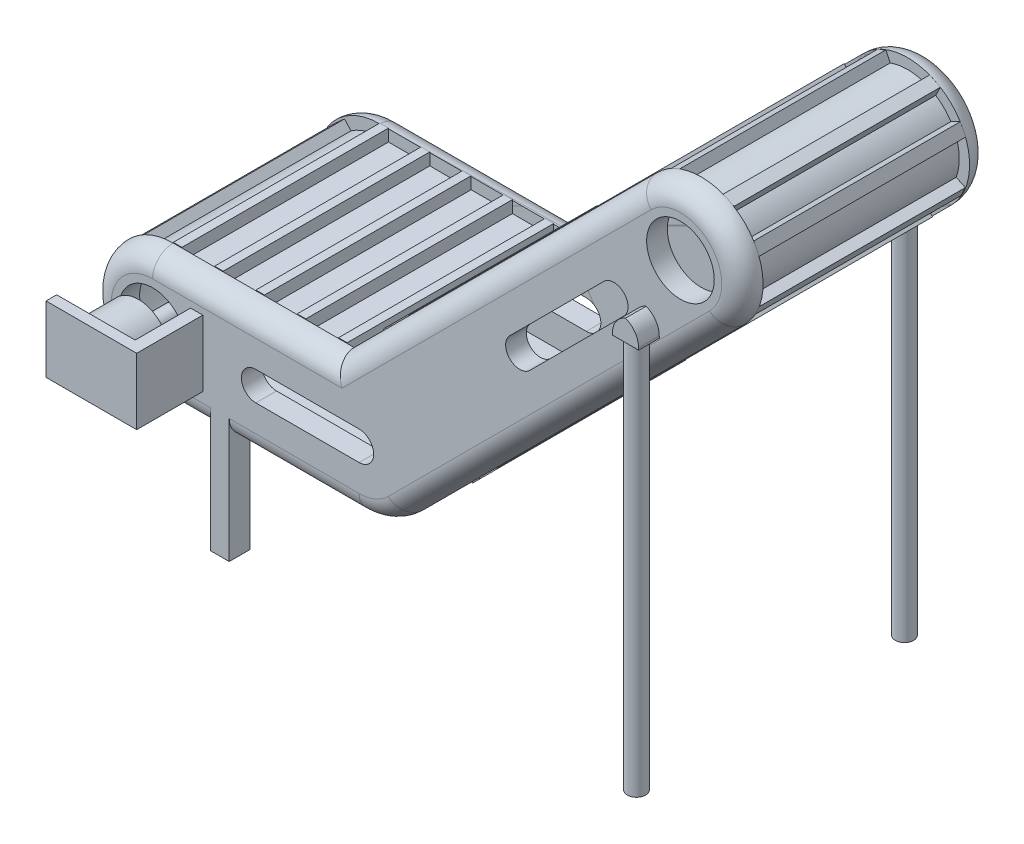
SolidWorks part; units mm, degrees
ref_plane "Front Plane" through (0, 0, 0) normal (0, 0, 1) x (1, 0, 0)
ref_plane "Top Plane" through (0, 0, 0) normal (0, 1, 0) x (1, 0, 0)
ref_plane "Right Plane" through (0, 0, 0) normal (1, 0, 0) x (0, 0, -1)
sketch "Sketch1" plane through (0, 0, 0) normal (0, 0, 1) x (1, 0, 0)
  line L0 (0, 0) -> (50, 0) construction
  line L1 (0, 15) -> (43.7868, 15)
  line L2 (0, -15) -> (50, -15)
  line L3 (50, 0) -> (127.7817, 77.7817) construction
  line L4 (43.7868, 15) -> (117.1751, 88.3883)
  line L5 (60.6066, -10.6066) -> (138.3883, 67.1751)
  line L6 (25, 0) -> (50, 0) construction
  line L7 (25, 3.5125) -> (50, 3.5125)
  line L8 (25, -3.5125) -> (50, -3.5125)
  line L9 (88.8909, 38.8909) -> (111.6659, 61.6659) construction
  line L10 (86.466, 41.3158) -> (109.241, 64.0908)
  line L11 (91.3158, 36.466) -> (114.0908, 59.241)
  arc A0 (0, 15) -> (0, -15) centre (0, 0) ccw
  arc A1 (50, -15) -> (60.6066, -10.6066) centre (50, 0) ccw
  arc A3 (138.3883, 67.1751) -> (117.1751, 88.3883) centre (127.7817, 77.7817) ccw
  arc A4 (50, -15) -> (60.6066, -10.6066) centre (50, 0) ccw
  circle A5 centre (0, 0) radius 8.1381
  circle A6 centre (127.7817, 77.7817) radius 8.1838
  arc A7 (25, 3.5125) -> (25, -3.5125) centre (25, 0) ccw
  arc A8 (50, -3.5125) -> (50, 3.5125) centre (50, 0) ccw
  arc A9 (86.466, 41.3158) -> (91.3158, 36.466) centre (88.8909, 38.8909) ccw
  arc A10 (114.0908, 59.241) -> (109.241, 64.0908) centre (111.6659, 61.6659) ccw
  point P3 (25, 0)
  point P10 (88.8909, 38.8909)
  point P17 (37.5, 0)
  point P22 (100.2784, 50.2784)
  dimension "D3" = 15
  dimension "D4" = 15
  dimension "D1" = 50
  dimension "D2" = 110
extrude "Boss-Extrude1" add sketch "Sketch1" along normal blind 5 contours L5 A3 L4 L1 A0 L2 A1 A10 L11 A9 L10 A8 L8 A7 L7 A6 A5
sketch "Sketch3" plane through (0, 15, 0) normal (0, 1, 0) x (1, 0, 0)
  line L0 (0, -5) -> (50, -5) construction
  line L1 (13.9802, -5) -> (18.5446, -5)
  line L2 (13.9802, -5) -> (13.9802, 0)
  line L3 (13.9802, 0) -> (18.5446, 0)
  line L4 (18.5446, -5) -> (18.5446, 0)
  line L5 (0, 0) -> (50, 0) construction
extrude "Boss-Extrude5" add sketch "Sketch3" against normal blind 55
fillet "Fillet1" radius 5 3 edges at (6.9901, -15, 5) (-15, 0, 5) (21.8934, 15, 5)
fillet "Fillet2" radius 5 5 edges at (34.2723, -15, 5) (55.7403, -13.8582, 5) (99.4975, 28.2843, 5) (138.3883, 88.3883, 5) (77.981, 49.1942, 5)
ref_plane "Plane2" through (0, 0, -25) normal (0, 0, 1) x (1, 0, 0)
mirror "Mirror6" about plane through (0, 0, -25) normal (0, 0, 1) of bodies 105
sketch "Sketch5" plane through (0, 0, -25) normal (0, 0, 1) x (1, 0, 0)
  line L0 (0, 0) -> (37.5139, 0) construction
  line L1 (2.0985, 12.2267) -> (10, 12.2267)
  line L2 (2.0985, -12.2286) -> (10, -12.2355)
  line L3 (50, 0) -> (127.7817, 77.7817) construction
  line L4 (49.3072, 16.934) -> (52.8392, 20.4682)
  line L5 (60.7195, -6.951) -> (65.1802, -2.4902)
  line L6 (0, 0) -> (37.5139, 0) construction
  line L7 (0, 10.7267) -> (37.5139, 10.7267)
  line L8 (0, -10.7267) -> (50.6802, -10.7267)
  line L9 (127.7817, 77.7817) -> (50, 0) construction
  line L11 (120.0072, 85.5563) -> (47.8481, 13.3972)
  line L12 (10, 12.2267) -> (10, 15.1579)
  line L14 (0, 12.2267) -> (0, 15.1579)
  line L15 (0, 15.1579) -> (2.0985, 15.1579)
  line L16 (2.0985, 12.2267) -> (2.0985, 15.1579)
  line L18 (12.0985, 12.2267) -> (12.0985, 15.1579)
  line L19 (10, 15.1579) -> (12.0985, 15.1579)
  line L20 (20, 12.2267) -> (20, 15.1579)
  line L22 (22.0985, 12.2267) -> (22.0985, 15.1579)
  line L23 (20, 15.1579) -> (22.0985, 15.1579)
  line L24 (30, 12.2267) -> (30, 15.1579)
  line L26 (32.0985, 12.2267) -> (32.0985, 15.1579)
  line L27 (30, 15.1579) -> (32.0985, 15.1579)
  line L28 (40, 12.2267) -> (40, 15.1579)
  line L29 (40, 12.2267) -> (40.4589, 12.2267)
  line L30 (42.0985, 12.2267) -> (42.0985, 15.1579)
  line L31 (40, 15.1579) -> (42.0985, 15.1579)
  line L32 (42.0985, -12.2267) -> (42.0985, -15.1579)
  line L33 (40, -15.1579) -> (42.0985, -15.1579)
  line L34 (40, -12.2267) -> (40, -15.1579)
  line L35 (30, -15.1579) -> (32.0985, -15.1579)
  line L36 (32.0985, -12.2267) -> (32.0985, -15.1579)
  line L37 (30, -12.2267) -> (30, -15.1579)
  line L38 (22.0985, -12.2267) -> (22.0985, -15.1579)
  line L39 (20, -15.1579) -> (22.0985, -15.1579)
  line L40 (20, -12.2267) -> (20, -15.1579)
  line L41 (12.0985, -12.2267) -> (12.0985, -15.1579)
  line L42 (10, -15.1579) -> (12.0985, -15.1579)
  line L43 (10, -12.2267) -> (10, -15.1579)
  line L44 (2.0985, -12.2267) -> (2.0985, -15.1579)
  line L45 (0, -12.2267) -> (0, -15.1579)
  line L46 (0, -15.1579) -> (2.0985, -15.1579)
  line L48 (47.5321, 15.1579) -> (46.0271, 16.662)
  line L49 (49.3072, 16.934) -> (47.8021, 18.4382)
  line L50 (46.0271, 16.662) -> (47.8021, 18.4382)
  line L52 (52.8392, 20.4682) -> (50.8757, 22.4305)
  line L53 (54.5966, 22.2267) -> (52.6331, 24.189)
  line L54 (50.8757, 22.4305) -> (52.6331, 24.189)
  line L56 (58.8352, 26.468) -> (56.9622, 28.3398)
  line L57 (62.0318, 29.6666) -> (60.1588, 31.5384)
  line L58 (56.9622, 28.3398) -> (60.1588, 31.5384)
  line L59 (67.1619, 34.7999) -> (65.2889, 36.6717)
  line L61 (65.2889, 36.6717) -> (67.1559, 38.5399)
  line L62 (69.0289, 36.6681) -> (67.1559, 38.5399)
  line L63 (74.4579, 42.1005) -> (72.5849, 43.9723)
  line L65 (72.5849, 43.9723) -> (74.7618, 46.1505)
  line L66 (76.6347, 44.2787) -> (74.7618, 46.1505)
  line L67 (81.8296, 49.4767) -> (79.9566, 51.3486)
  line L69 (79.9566, 51.3486) -> (81.7542, 53.1474)
  line L70 (83.6272, 51.2755) -> (81.7542, 53.1474)
  line L71 (88.8909, 56.5425) -> (87.0179, 58.4143)
  line L73 (87.0179, 58.4143) -> (88.8008, 60.1983)
  line L74 (90.6737, 58.3265) -> (88.8008, 60.1983)
  line L75 (96.4729, 64.1292) -> (94.5999, 66.001)
  line L77 (94.5999, 66.001) -> (96.2798, 67.682)
  line L78 (98.1528, 65.8101) -> (96.2798, 67.682)
  line L79 (104.322, 71.9833) -> (102.449, 73.8551)
  line L81 (102.449, 73.8551) -> (104.2537, 75.6608)
  line L82 (106.1266, 73.789) -> (104.2537, 75.6608)
  line L83 (112.3034, 79.9696) -> (110.4304, 81.8415)
  line L85 (110.4304, 81.8415) -> (112.418, 83.8303)
  line L86 (114.291, 81.9585) -> (112.418, 83.8303)
  line L88 (121.4099, 88.5298) -> (120.3652, 90.7497)
  line L89 (123.5609, 89.5421) -> (122.5162, 91.7619)
  line L90 (120.3652, 90.7497) -> (122.5162, 91.7619)
  line L92 (132.0026, 89.5421) -> (133.1346, 91.8248)
  line L93 (134.589, 88.2595) -> (135.7209, 90.5422)
  line L94 (133.1346, 91.8248) -> (135.7209, 90.5422)
  line L96 (-6.9861, 10.0343) -> (-8.5357, 11.76)
  line L97 (-9.2272, 8.022) -> (-10.7767, 9.7476)
  line L98 (-8.5357, 11.76) -> (-10.7767, 9.7476)
  line L100 (-12.1096, 1.6884) -> (-15.5831, 1.6884)
  line L101 (-12.1096, -1.6884) -> (-15.5831, -1.6884)
  line L102 (-15.5831, 1.6884) -> (-15.5831, -1.6884)
  line L104 (-10.7267, -5.8677) -> (-15.0566, -8.8817)
  line L105 (-9.2272, -8.022) -> (-13.5571, -11.0359)
  line L106 (-15.0566, -8.8817) -> (-13.5571, -11.0359)
  line L107 (65.1579, -2.4679) -> (66.662, -3.9729)
  line L108 (66.662, -3.9729) -> (68.4382, -2.1979)
  line L109 (66.934, -0.6928) -> (68.4382, -2.1979)
  line L110 (70.4682, 2.8392) -> (72.4305, 0.8757)
  line L111 (72.4305, 0.8757) -> (74.189, 2.6331)
  line L112 (72.2267, 4.5966) -> (74.189, 2.6331)
  line L113 (76.468, 8.8352) -> (78.3398, 6.9622)
  line L114 (78.3398, 6.9622) -> (81.5384, 10.1588)
  line L115 (79.6666, 12.0318) -> (81.5384, 10.1588)
  line L116 (99.4767, 31.8296) -> (101.3486, 29.9566)
  line L117 (101.3486, 29.9566) -> (103.1474, 31.7542)
  line L118 (101.2755, 33.6272) -> (103.1474, 31.7542)
  line L119 (106.5425, 38.8909) -> (108.4143, 37.0179)
  line L120 (108.4143, 37.0179) -> (110.1983, 38.8008)
  line L121 (108.3265, 40.6737) -> (110.1983, 38.8008)
  line L122 (114.1292, 46.4729) -> (116.001, 44.5999)
  line L123 (116.001, 44.5999) -> (117.682, 46.2798)
  line L124 (115.8101, 48.1528) -> (117.682, 46.2798)
  line L125 (121.9833, 54.322) -> (123.8551, 52.449)
  line L126 (123.8551, 52.449) -> (125.6608, 54.2537)
  line L127 (123.789, 56.1266) -> (125.6608, 54.2537)
  line L128 (129.9696, 62.3034) -> (131.8415, 60.4304)
  line L129 (131.8415, 60.4304) -> (133.8303, 62.418)
  line L130 (131.9585, 64.291) -> (133.8303, 62.418)
  line L131 (138.5298, 71.4099) -> (140.7497, 70.3652)
  line L132 (140.7497, 70.3652) -> (141.7619, 72.5162)
  line L133 (139.5421, 73.5609) -> (141.7619, 72.5162)
  line L134 (138.2595, 84.589) -> (140.5422, 85.7209)
  line L135 (141.8248, 83.1346) -> (140.5422, 85.7209)
  line L136 (139.5421, 82.0026) -> (141.8248, 83.1346)
  line L138 (84.7999, 17.1619) -> (86.6717, 15.2889)
  line L139 (86.6717, 15.2889) -> (88.5399, 17.1559)
  line L140 (86.6681, 19.0289) -> (88.5399, 17.1559)
  line L141 (92.1005, 24.4579) -> (93.9723, 22.5849)
  line L142 (93.9723, 22.5849) -> (96.1505, 24.7618)
  line L143 (94.2787, 26.6347) -> (96.1505, 24.7618)
  line L144 (58.8352, -8.8352) -> (60.6066, -10.6066)
  line L146 (60.6066, -10.6066) -> (62.4909, -8.7223)
  line L147 (60.7195, -6.951) -> (62.4909, -8.7223)
  line L148 (60.6066, -10.6066) -> (57.0711, -7.0711) construction
  line L149 (60.6066, -10.6066) -> (138.3883, 67.1751) construction
  line L150 (49.993, -12.2705) -> (50, -15)
  line L151 (52.3888, -12.2644) -> (52.548, -12.264)
  line L152 (50, -15) -> (52.5549, -14.9935)
  line L153 (52.548, -12.264) -> (52.5549, -14.9935)
  line L154 (50, -15) -> (50, -10) construction
  line L155 (12.0985, 12.2267) -> (20, 12.2267)
  line L156 (32.0985, 12.2267) -> (40.4589, 12.2267)
  line L157 (22.0985, 12.2267) -> (30, 12.2267)
  line L158 (54.5966, 22.2267) -> (58.8352, 26.468)
  line L159 (62.0318, 29.6666) -> (67.1619, 34.7999)
  line L160 (69.0289, 36.6681) -> (74.4579, 42.1005)
  line L161 (76.6347, 44.2787) -> (81.8296, 49.4767)
  line L162 (83.6272, 51.2755) -> (88.8909, 56.5425)
  line L163 (12.0985, -12.2373) -> (20, -12.2442)
  line L164 (22.0985, -12.2461) -> (30, -12.253)
  line L165 (32.0985, -12.2548) -> (40, -12.2618)
  line L166 (42.0985, -12.2636) -> (49.993, -12.2705)
  line L167 (66.9558, -0.7146) -> (70.4889, 2.8185)
  line L168 (72.2469, 4.5764) -> (76.4868, 8.8164)
  line L169 (79.6844, 12.014) -> (84.8161, 17.1457)
  line L170 (86.6837, 19.0133) -> (92.1144, 24.444)
  line L171 (94.2919, 26.6215) -> (99.4884, 31.8179)
  line L172 (101.2866, 33.6162) -> (106.5519, 38.8815)
  line L173 (108.3353, 40.6649) -> (114.1363, 46.4658)
  line L174 (115.8167, 48.1462) -> (121.9878, 54.3174)
  line L175 (123.793, 56.1226) -> (129.9717, 62.3013)
  line L176 (131.9599, 64.2895) -> (136.617, 68.9465)
  line L177 (90.6737, 58.3265) -> (96.4729, 64.1292)
  line L178 (98.1528, 65.8101) -> (104.322, 71.9833)
  line L179 (106.1266, 73.789) -> (112.3034, 79.9696)
  line L180 (114.291, 81.9585) -> (118.9287, 86.5991)
  line L181 (57.7513, -7.7978) -> (135.5563, 70.0072)
  arc A1 (0, 12.2267) -> (-6.9861, 10.0343) centre (0, 0) ccw
  arc A4 (136.617, 68.9465) -> (138.5298, 71.4099) centre (127.7817, 77.7817) ccw
  arc A5 (47.632, -12.2684) -> (49.9936, -12.4949) centre (50, 0) ccw
  arc A6 (0, 10.7267) -> (0, -10.7267) centre (0, 0) ccw
  arc A7 (39.2027, 10.593) -> (37.5139, 10.7267) centre (37.5139, 0) ccw
  arc A8 (135.5563, 70.0072) -> (120.0072, 85.5563) centre (127.7817, 77.7817) ccw
  arc A10 (47.8481, 13.3972) -> (39.2027, 10.593) centre (40.777, 20.4682) cw
  arc A11 (47.5321, 15.1579) -> (42.0985, 12.3621) centre (40.4589, 22.2267) cw
  arc A12 (57.7513, -7.7978) -> (50.6802, -10.7267) centre (50.6802, -0.7267) cw
  arc A13 (50, -15) -> (60.6066, -10.6066) centre (50, 0) ccw construction
  arc A14 (52.3888, -12.2644) -> (58.8352, -8.8352) centre (50, 0) ccw
  arc A15 (-9.2272, 8.022) -> (-12.1096, 1.6884) centre (0, 0) ccw
  arc A16 (-12.1096, -1.6884) -> (-10.7267, -5.8677) centre (0, 0) ccw
  arc A17 (-9.2272, -8.022) -> (0, -12.2267) centre (0, 0) ccw
  arc A18 (139.5421, 73.5609) -> (139.5421, 82.0026) centre (127.7817, 77.7817) ccw
  arc A19 (121.4099, 88.5298) -> (118.9287, 86.5991) centre (127.7817, 77.7817) ccw
  arc A20 (132.0026, 89.5421) -> (123.5609, 89.5421) centre (127.7817, 77.7817) ccw
  arc A21 (138.2595, 84.589) -> (134.589, 88.2595) centre (127.7817, 77.7817) ccw
  point P4 (25, 0)
  point P6 (18.7569, 0)
  point P12 (88.8909, 38.8909)
  point P21 (88.8909, 38.8909)
  dimension "D3" = 10
  dimension "D4" = 10
  dimension "D5" = 10
  dimension "D1" = 1.5
  dimension "D6" = 5
extrude "Boss-Extrude6" add sketch "Sketch5" against normal up to surface and the other way up to surface separate body contours L134 A21 L93 L94 L92 A20 L89 L90 L88 A19 L180 L86 L85 L83 L179 L82 L81 L79 L178 L78 L77 L75 L177 L74 L73 L71 L162 L70 L69 L67 L161 L66 L65 L63 L160 L62 L61 L59 L159 L57 L58 L56 L158 L53 L54 L52 L4 L49 L50 L48 A11
sketch "Sketch6" plane through (0, 0, 5) normal (0, 0, 1) x (1, 0, 0)
  line L1 (116.3232, 58.8688) -> (122.6501, 58.8688)
  line L2 (116.3232, 58.8688) -> (116.3232, 64.3521)
  line L3 (116.3232, 64.3521) -> (122.6501, 64.3521)
  line L4 (122.6501, 58.8688) -> (122.6501, 64.3521)
  line L5 (116.3232, 58.8688) -> (122.6501, 64.3521) construction
  line L6 (116.3232, 64.3521) -> (122.6501, 58.8688) construction
  point P0 (119.4866, 61.6104)
extrude "Boss-Extrude7" add sketch "Sketch6" along normal blind 5
fillet "Fillet4" radius 5 2 edges at (116.3232, 64.3521, 7.5) (122.6501, 64.3521, 7.5)
sketch "Sketch7" plane through (0, 58.8688, 0) normal (0, -1, 0) x (1, 0, 0)
  circle A0 centre (119.5759, 7.4319) radius 2.2161
extrude "Boss-Extrude8" add sketch "Sketch7" along normal blind 95
mirror "Mirror8" about plane through (0, 0, -25) normal (0, 0, 1) of bodies 110
sketch "Sketch8" plane through (0, 0, 5) normal (0, 0, 1) x (1, 0, 0)
  line L1 (9.1883, -7.5633) -> (12.1408, -7.5633)
  line L2 (9.1883, -7.5633) -> (9.1883, 8.4648)
  line L3 (9.1883, 8.4648) -> (12.1408, 8.4648)
  line L4 (12.1408, -7.5633) -> (12.1408, 8.4648)
extrude "Boss-Extrude12" add sketch "Sketch8" along normal blind 16
sketch "Sketch10" plane through (9.1883, 0, 0) normal (-1, 0, 0) x (0, 0, 1)
  line L0 (21, -7.5633) -> (5, -7.5633) construction
  line L1 (21, 8.4648) -> (18.4189, 8.4648)
  line L2 (21, 8.4648) -> (21, -7.5633)
  line L3 (21, -7.5633) -> (18.4189, -7.5633)
  line L4 (18.4189, 8.4648) -> (18.4189, -7.5633)
extrude "Boss-Extrude13" add sketch "Sketch10" along normal blind 19
sketch "Sketch11" plane through (0, 0, 18.4189) normal (0, 0, -1) x (-1, 0, 0)
  circle A0 centre (0, 0) radius 7.3979
extrude "Boss-Extrude14" add sketch "Sketch11" along normal blind 10
sketch "Sketch12" plane through (0, 0, 8.4189) normal (0, 0, -1) x (-1, 0, 0)
  circle A0 centre (0, 0) radius 2.2909
extrude "Boss-Extrude15" add sketch "Sketch12" along normal up to vertex (8.4189 mm away) up to point (0, 0, 0)
